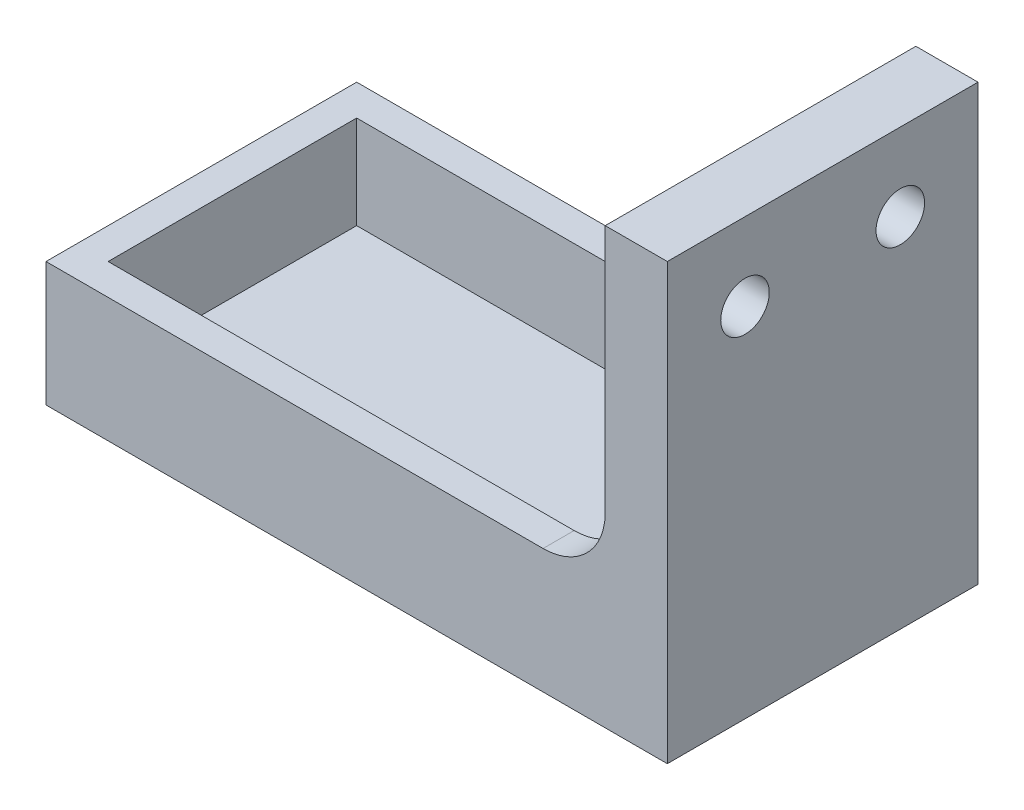
SolidWorks part; units mm, degrees
ref_plane "Front Plane" through (0, 0, 0) normal (0, 0, 1) x (1, 0, 0)
ref_plane "Top Plane" through (0, 0, 0) normal (0, 1, 0) x (1, 0, 0)
ref_plane "Right Plane" through (0, 0, 0) normal (1, 0, 0) x (0, 0, -1)
sketch "Sketch1" plane through (0, 0, 0) normal (0, 1, 0) x (1, 0, 0)
  line L1 (-22.86, 25.4) -> (22.86, 25.4)
  line L2 (-22.86, 25.4) -> (-22.86, 0)
  line L3 (-22.86, 0) -> (22.86, 0)
  line L4 (22.86, 25.4) -> (22.86, 0)
  dimension "D1" = 45.72
  dimension "D2" = 25.4
extrude "Boss-Extrude1" add sketch "Sketch1" along normal blind 10.16
shell "Shell1" thickness 2.54 removed face at (0, 10.16, -12.7)
sketch "Sketch2" plane through (22.86, 0, 0) normal (1, 0, 0) x (0, 0, -1)
  line L0 (0, 0) -> (25.4, 0) construction
  line L1 (25.4, 0) -> (0, 0)
  line L2 (25.4, 0) -> (25.4, 35.56)
  line L3 (25.4, 35.56) -> (0, 35.56)
  line L4 (0, 0) -> (0, 35.56)
  line L6 (0, 10.16) -> (25.4, 10.16) construction
  line L7 (0, 10.16) -> (0, 0) construction
  point P6 (15.4047, 0)
  point P7 (12.7, 0)
  point P8 (12.7, 0)
  dimension "D1" = 25.4
extrude "Boss-Extrude2" add sketch "Sketch2" along normal blind 5.08
fillet "Fillet1" radius 5.08 1 edges at (22.86, 10.16, -12.7)
sketch "Sketch3" plane through (22.86, 0, 0) normal (-1, 0, 0) x (0, 0, 1)
  line L0 (-25.4, 15.24) -> (-25.4, 35.56) construction
  line L1 (-25.4, 35.56) -> (0, 35.56) construction
  line L2 (0, 35.56) -> (0, 15.24) construction
  circle A0 centre (-19.05, 29.21) radius 1.9844
  circle A1 centre (-6.35, 29.21) radius 1.9844
  point P4 (0, 0)
  dimension "D1" = 3.9688
  dimension "D2" = 6.35
  dimension "D3" = 6.35
  dimension "D4" = 6.35
  dimension "D5" = 6.35
extrude "Cut-Extrude1" cut sketch "Sketch3" against normal through all both and the other way through all
